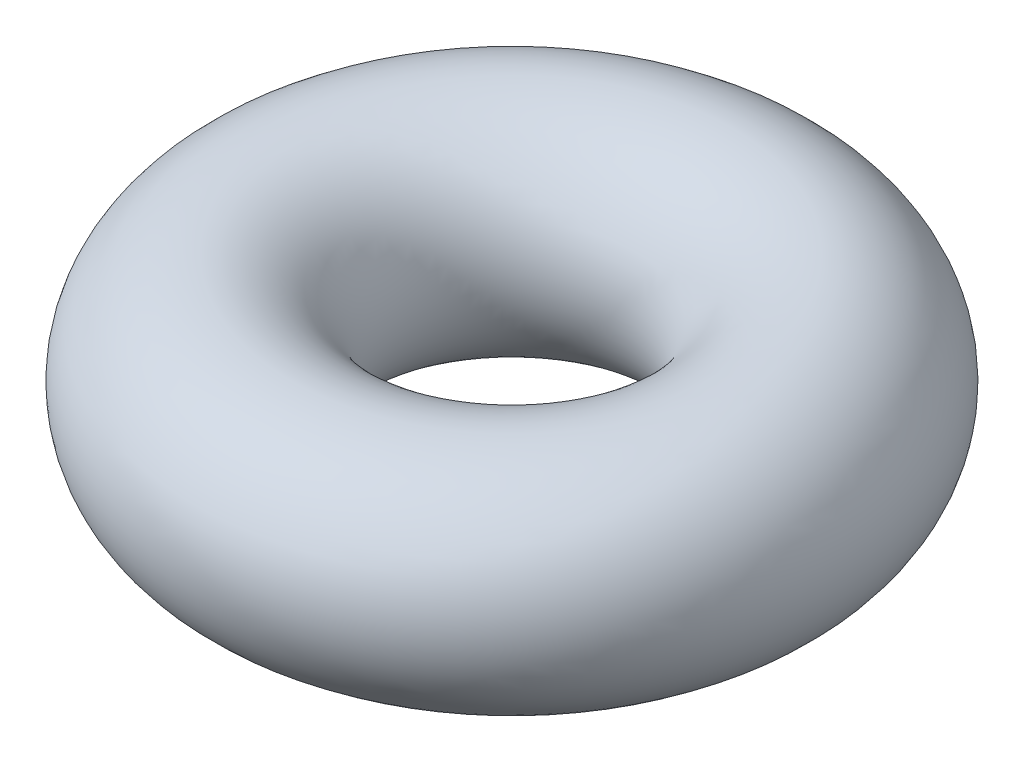
SolidWorks part; units mm, degrees
ref_plane "Front Plane" through (0, 0, 0) normal (0, 0, 1) x (1, 0, 0)
ref_plane "Top Plane" through (0, 0, 0) normal (0, 1, 0) x (1, 0, 0)
ref_plane "Right Plane" through (0, 0, 0) normal (1, 0, 0) x (0, 0, -1)
sketch "Sketch1" plane through (0, 0, 0) normal (0, 0, 1) x (1, 0, 0)
  line L0 (-0.889, 0) -> (0.889, 0) construction
  line L1 (-2.667, 0) -> (2.667, 0) construction
  circle A0 centre (-1.778, 0) radius 0.889 construction
  dimension "Width" = 1.778
  dimension "ID" = 1.778
  dimension "OD" = 5.334
sketch "Sketch3" plane through (0, 0, 0) normal (1, 0, 0) x (0, 0, -1)
  line L0 (0, 0) -> (-0.5927, 0) construction
  line L1 (-0.5927, 0) -> (-0.5927, 0.889) construction
  point P0 (-0.5927, 0.889)
  dimension "D1" = 0.5927
  dimension "D2" = 0.889
sketch "Sketch2" plane through (0, 0, 0) normal (0, 0, 1) x (1, 0, 0)
  line L0 (0, 0) -> (0, 0.889) construction
  line L1 (-0.889, 0) -> (0.889, 0) construction
  circle A0 centre (-1.778, 0) radius 0.889 construction
  circle A1 centre (-1.778, 0) radius 0.889
  point P7 (-1.778, 0.889)
revolve "Revolve1" add sketch "Sketch2" angle 360 about L0
ref_axis "Center Axis 1" through (0, 0.9779, 0) along (0, -1, 0)
sketch "Sketch4" plane through (0, 0, 0) normal (0, 1, 0) x (1, 0, 0)
  circle A0 centre (0, 0) radius 0.5678
equation "\"D1@Sketch3\"=\"ID@Sketch1\"/3"
equation "\"D2@Sketch3\"=\"Width@Sketch1\"/2"
